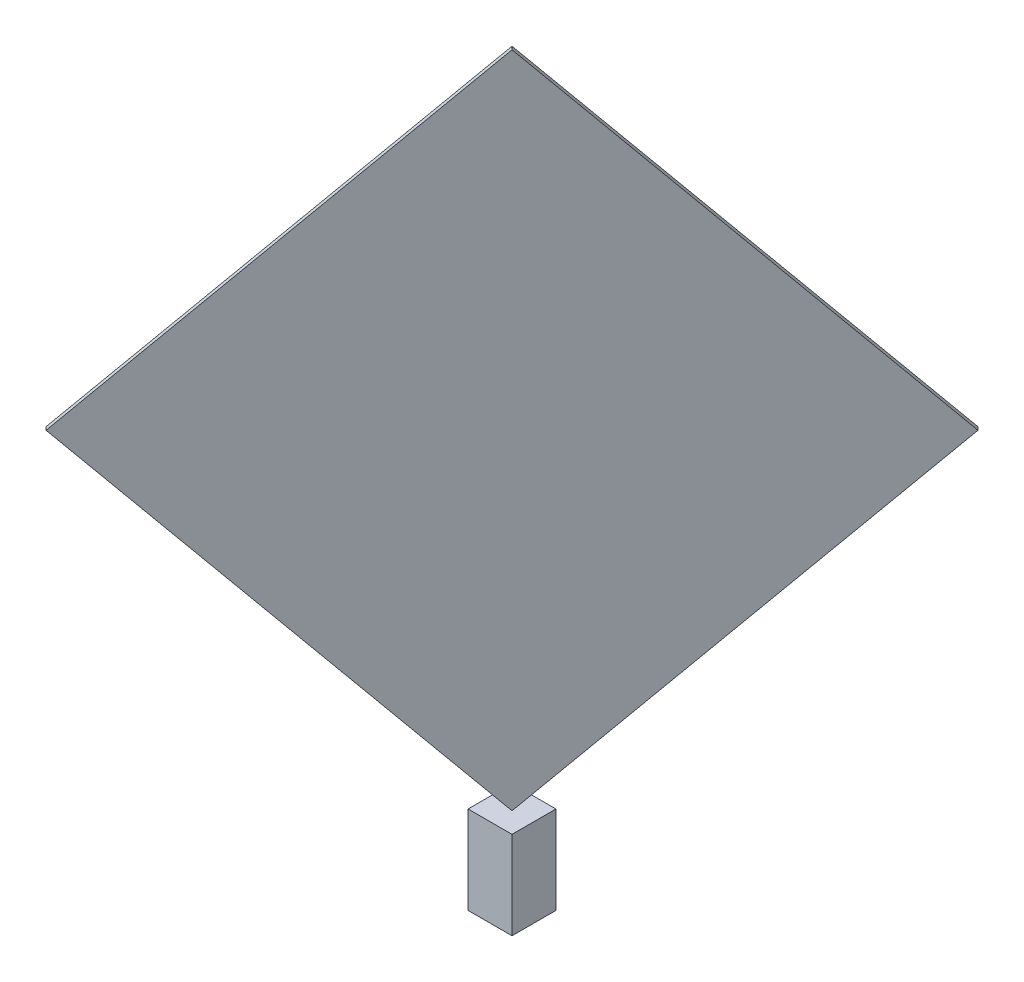
SolidWorks part; units mm, degrees
ref_plane "Front Plane" through (0, 0, 0) normal (0, 0, 1) x (1, 0, 0)
ref_plane "Top Plane" through (0, 0, 0) normal (0, 1, 0) x (1, 0, 0)
ref_plane "Right Plane" through (0, 0, 0) normal (1, 0, 0) x (0, 0, -1)
sketch "Sketch1" plane through (0, 0, 0) normal (0, 1, 0) x (1, 0, 0)
  line L1 (-51.8072, 78.3133) -> (48.1928, 78.3133)
  line L2 (-51.8072, 78.3133) -> (-51.8072, -21.6867)
  line L3 (-51.8072, -21.6867) -> (48.1928, -21.6867)
  line L4 (48.1928, 78.3133) -> (48.1928, -21.6867)
  dimension "D1" = 100
  dimension "D2" = 100
extrude "Boss-Extrude1" add sketch "Sketch1" along normal blind 200
ref_plane "Plane1" through (-15.0602, 0, -15.0602) normal (-0.7071, 0, -0.7071) x (-0.7071, 0, 0.7071)
sketch "Sketch2" plane through (-15.0602, 0, -15.0602) normal (-0.7071, 0, -0.7071) x (-0.7071, 0, 0.7071)
  line L0 (-89.4533, 200) -> (-18.7426, 200)
  line L1 (-89.4533, 200) -> (-18.7426, 200)
  line L2 (-18.7426, 200) -> (51.9681, 200)
  line L3 (-18.7426, 200) -> (51.9681, 200)
  line L4 (51.9681, 200) -> (51.9681, 0)
  line L5 (51.9681, 200) -> (51.9681, 0)
  line L6 (51.9681, 0) -> (-18.7426, 0)
  line L7 (51.9681, 0) -> (-18.7426, 0)
  line L8 (-18.7426, 0) -> (-89.4533, 0)
  line L9 (-18.7426, 0) -> (-89.4533, 0)
  line L10 (-89.4533, 0) -> (-89.4533, 200)
  line L11 (-89.4533, 0) -> (-89.4533, 200)
  line L12 (-18.7426, 200) -> (731.2574, 950)
  line L13 (-18.7426, 200) -> (-768.7426, 950)
  line L14 (731.2574, 950) -> (-18.7426, 1700)
  line L15 (-768.7426, 950) -> (-18.7426, 1700)
  dimension "D1" = 45
  dimension "D2" = 1500
extrude "Boss-Extrude2" add sketch "Sketch2" along normal blind 5 and the other way blind 5 separate body contours L12 L13 L15 L14
